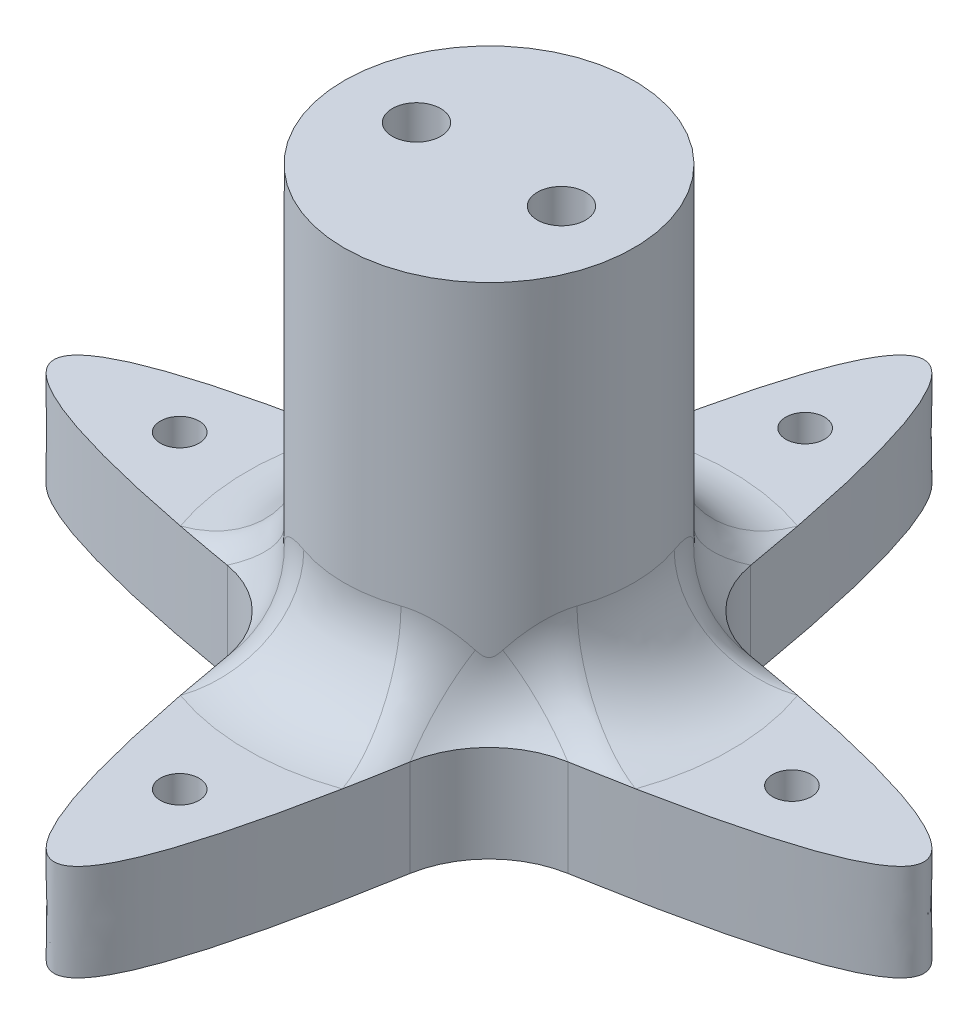
SolidWorks part; units mm, degrees
material "1060 Alloy"
ref_plane "Front Plane" through (0, 0, 0) normal (0, 0, 1) x (1, 0, 0)
ref_plane "Top Plane" through (0, 0, 0) normal (0, 1, 0) x (1, 0, 0)
ref_plane "Right Plane" through (0, 0, 0) normal (1, 0, 0) x (0, 0, -1)
sketch "Sketch13" plane through (0, 0, 0) normal (0, 1, 0) x (1, 0, 0)
  line L0 (-19.5167, 19.5167) -> (19.5167, -19.5167) construction
  line L1 (-16.3929, -16.3929) -> (16.3929, 16.3929) construction
  line L2 (-40.2074, 0) -> (40.2556, 0) construction
  spline S0 degree 2 poles (-10.6066, 10.6066) (-0.0005, 79.3951) (10.61, 10.6032) knots 0 0 0 1 1 1
  spline S1 degree 2 poles (10.61, 10.6032) (79.3917, 0.0005) (10.6066, -10.6066) knots 0 0 0 1 1 1
  spline S2 degree 2 poles (10.6066, -10.6066) (0, -79.3934) (-10.6066, -10.6066) knots 0 0 0 1 1 1
  spline S3 degree 2 poles (-10.6066, -10.6066) (-79.3934, 0) (-10.6066, 10.6066) knots 0 0 0 1 1 1
  point P6 (0, 0)
  point P9 (0, 0)
  point P12 (0, 0)
  point P27 (0, 0)
  dimension "D2" = 90
  dimension "D3" = 45
sketch "Sketch15" plane through (0, 0, 0) normal (0, 1, 0) x (1, 0, 0)
  circle A0 centre (0, 0) radius 15
  dimension "D1" = 30
extrude "Boss-Extrude5" add sketch "Sketch15" along normal blind 50
extrude "Boss-Extrude6" add sketch "Sketch13" along normal blind 10
fillet "Fillet1" radius 10 4 edges at (-10.6066, 5, 10.6066) (10.6066, 5, 10.6066) (10.61, 5, -10.6032) (-10.6066, 5, -10.6066)
sketch "Sketch16" plane through (0, 50, 0) normal (0, 1, 0) x (1, 0, 0)
  circle A0 centre (-7.5, 0) radius 2.5
  circle A1 centre (7.5, 0) radius 2.5
  dimension "D1" = 5
  dimension "D2" = 5
  dimension "D3" = 7.5
  dimension "D4" = 7.5
extrude "Cut-Extrude3" cut sketch "Sketch16" against normal through all
sketch "Sketch17" plane through (0, 10, 0) normal (0, 1, 0) x (1, 0, 0)
  circle A0 centre (0, 32.7096) radius 2
  circle A1 centre (31.3429, 0) radius 2
  circle A2 centre (0, -32) radius 2
  circle A3 centre (-32, 0) radius 2
  parabola Q0 (9.4675, 17.612) -> (-9.4644, 17.6156) focus (0.0003, 44.182) apex (0.0003, 45) construction
  parabola Q1 (17.6154, -9.4643) -> (17.619, 9.4612) focus (44.1825, -0.0003) apex (45, -0.0003) construction
  parabola Q2 (-9.4644, -17.6155) -> (9.4644, -17.6154) focus (0, -44.1823) apex (0, -45) construction
  parabola Q3 (-17.6156, 9.4643) -> (-17.6155, -9.4644) focus (-44.1823, 0) apex (-45, 0) construction
  point P2 (0.0007, 45.7096)
  point P10 (44.3429, -0.0006)
  point P17 (0, -45)
  point P24 (-45, 0)
  dimension "D1" = 4
  dimension "D3" = 13
  dimension "D4" = 13
  dimension "D5" = 13
  dimension "D6" = 4
  dimension "D7" = 4
  dimension "D8" = 4
  dimension "D2" = 13
extrude "Cut-Extrude4" cut sketch "Sketch17" against normal through all
fillet "Fillet2" radius 10 4 edges at (0, 10, 15) (15, 10, 0.0024) (0.0024, 10, -15) (-15, 10, 0)
